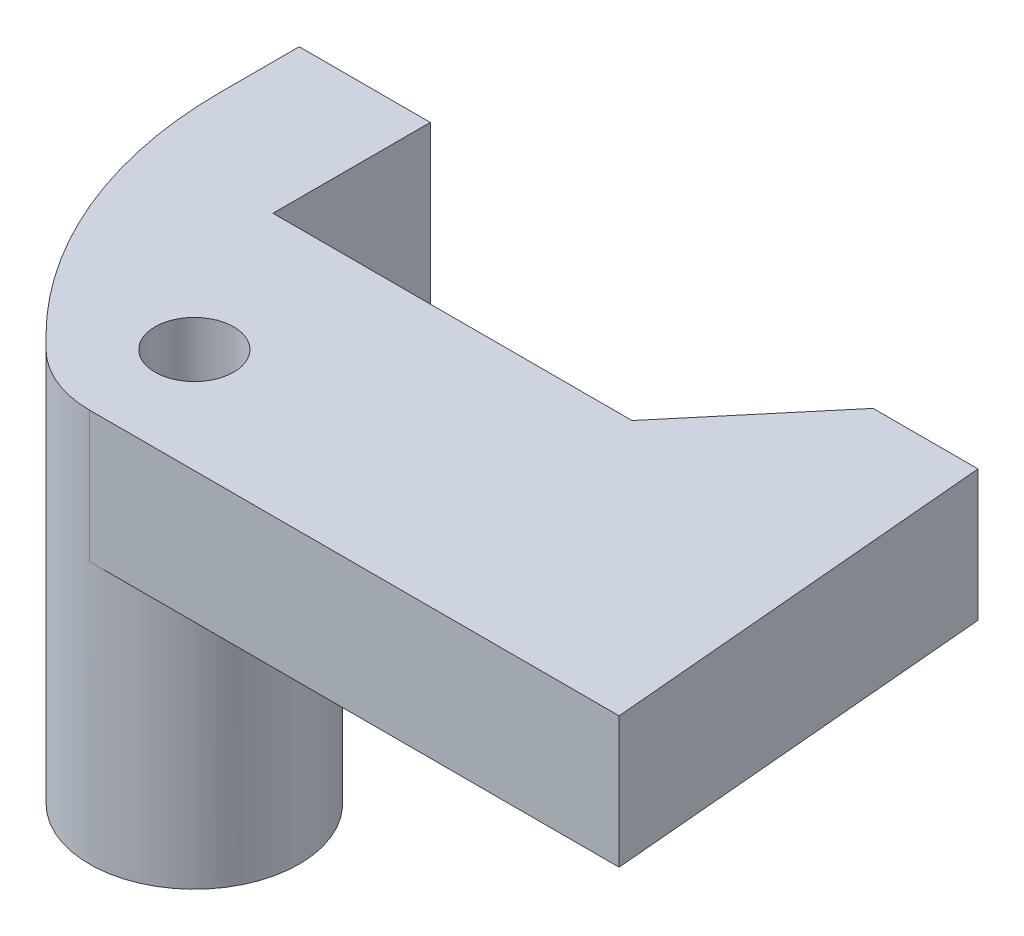
SolidWorks part; units mm, degrees
ref_plane "Front Plane" through (0, 0, 0) normal (0, 0, 1) x (1, 0, 0)
ref_plane "Top Plane" through (0, 0, 0) normal (0, 1, 0) x (1, 0, 0)
ref_plane "Right Plane" through (0, 0, 0) normal (1, 0, 0) x (0, 0, -1)
sketch "Sketch1" plane through (0, 0, 0) normal (0, 1, 0) x (1, 0, 0)
  line L0 (0, 32.3882) -> (0, 7) construction
  line L1 (0, 7) -> (6, 7) construction
  line L2 (6, 7) -> (39, 22.3882) construction
  line L3 (39, 22.3882) -> (72, 7) construction
  line L4 (72, 7) -> (78, 7) construction
  line L5 (78, 7) -> (78, 32.3882) construction
  line L6 (78, 32.3882) -> (0, 32.3882) construction
  line L7 (-11, 13) -> (-11, 16)
  line L8 (11.8877, 15) -> (15.8877, 15)
  line L9 (-3, 0) -> (17.2, 0)
  line L10 (17.5, 15.9916) -> (17.5, 0.8497) construction
  line L11 (17.2, 0) -> (15.8877, 15)
  line L12 (11.8877, 15) -> (7.6922, 10)
  line L13 (7.6922, 10) -> (-6, 10)
  line L14 (-11, 16) -> (-6, 16)
  line L15 (-6, 16) -> (-6, 10)
  line L16 (-5.8284, 1.1716) -> (-6.2929, 1.636)
  line L19 (-3, 4) -> (-3, 0) construction
  circle A0 centre (-3, 4) radius 1.5
  circle A1 centre (-3, 4) radius 4 construction
  circle A2 centre (39, -0.5) radius 21 construction
  circle A3 centre (18.4662, -10) radius 21 construction
  arc A4 (-11, 13) -> (-6.2929, 1.636) centre (5.0711, 13) ccw
  arc A5 (-3, 0) -> (-5.8284, 1.1716) centre (-3, 4) cw
  dimension "D5" = 3
  dimension "D11" = 3
  dimension "D13" = 42
  dimension "D3" = 130
  dimension "D23" = 4
  dimension "D24" = 8
  dimension "D1" = 6
  dimension "D2" = 78
  dimension "D4" = 10
  dimension "D6" = 7
  dimension "D7" = 3
  dimension "D8" = 85
  dimension "D9" = 20.2
  dimension "D10" = 17.5
  dimension "D12" = 15
  dimension "D14" = 4
  dimension "D15" = 3
  dimension "D16" = 50
  dimension "D17" = 4
  dimension "D18" = 10
  dimension "D19" = 0.5
  dimension "D20" = 6
  dimension "D21" = 5
  dimension "D25" = 10
  dimension "D26" = 135
extrude "Boss-Extrude1" add sketch "Sketch1" along normal blind 5
sketch "Sketch2" plane through (0, 0, 0) normal (0, -1, 0) x (1, 0, 0)
  line L0 (-5.8284, -1.1716) -> (-6.2929, -1.636)
  line L3 (-11, -13) -> (-11, -16)
  line L4 (-11, -16) -> (-6, -16)
  line L5 (-6, -16) -> (-6, -8)
  line L6 (-6, -8) -> (-3, -8)
  line L7 (-11, -16) -> (-11, -13) construction
  arc A0 (-3, 0) -> (-3, -8) centre (-3, -4) cw
  circle A1 centre (-3, -4) radius 1.5
  arc A2 (-3, 0) -> (-5.8284, -1.1716) centre (-3, -4) ccw
  arc A3 (-6.2929, -1.636) -> (-11, -13) centre (5.0711, -13) ccw construction
  arc A4 (-6.2929, -1.636) -> (-11, -13) centre (5.0711, -13) ccw
  dimension "D2" = 3
extrude "Boss-Extrude2" add sketch "Sketch2" along normal blind 10
